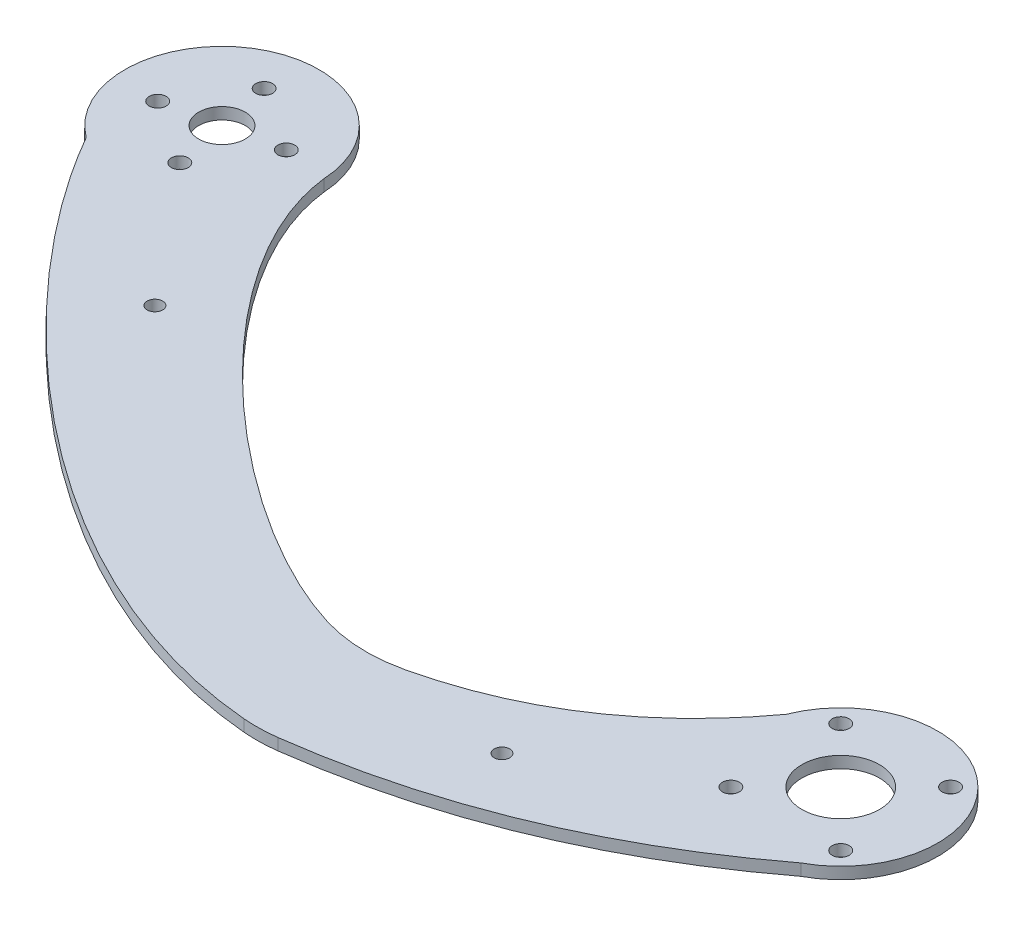
SolidWorks part; units mm, degrees
material "1060 Alloy"
ref_plane "Front" through (0, 0, 0) normal (0, 0, 1) x (1, 0, 0)
ref_plane "Top" through (0, 0, 0) normal (0, 1, 0) x (1, 0, 0)
ref_plane "Right" through (0, 0, 0) normal (1, 0, 0) x (0, 0, -1)
sketch "Sketch2" plane through (0, 0, 0) normal (0, 1, 0) x (1, 0, 0)
  point P0 (0, 0)
  line B0 (-70.9851, 36.1523) -> (-113.5823, 33.9244)
  arc B1 (5.8927, -11.0239) -> (-11.6176, 4.6132) centre (0, 0) ccw
  arc B2 (-101.0993, 34.5773) -> (-120.9882, 23.8546) centre (-113.5823, 33.9244) ccw
  spline B3 degree 3 poles (-44.5149, -15.6481) (-60.4932, -16.621) (-98.7194, 13.994) (-101.0993, 34.5773) knots 0 0 0 0 1 1 1 1
  spline B4 degree 2 poles (5.8927, -11.0239) (-16.2083, -27.8197) (-43.715, -30.9419) knots 0 0 0 1 1 1
  spline B5 degree 3 poles (-43.715, -30.9419) (-74.6559, -29.7722) (-107.9347, 0.9093) (-120.9882, 23.8546) knots 0 0 0 0 1 1 1 1
  spline B6 degree 2 poles (-44.5149, -15.6481) (-23.755, -12.0499) (-11.6176, 4.6132) knots 0 0 0 1 1 1
sketch_block_instance "Block5-1"
sketch_block "Block5" parameters "D1"=25, "D14"=79.1954, "D15"=48.0238, "D17"=92.8889, "D18"=42.1388, "D19"=62.1612, "D2"=5.3089, "D3"=16.6697, "D4"=25.1002, "D5"=50.5803, "D6"=74.3089, "D7"=104.4643, "D8"=116.9643, "D9"=124.8861, "D10"=135.8089, "D11"=34.5967, "D12"=39.8104, "D13"=51.127, "D16"=68.4269
extrude "Boss-Extrude1" add sketch "Sketch2" along normal blind 1.5 contours B5 B4 B1 B6 B3 B2 region at (-18.1336, 0, 22.9214)
fillet "Fillet2" radius 20 1 edges at (-44.5149, 0.75, 15.6481)
fillet "Fillet3" radius 20 1 edges at (-43.715, 0.75, 30.9419)
ref_plane "Plane1" through (0, 1.5, 0) normal (0, 1, 0) x (1, 0, 0)
sketch "Sketch3" plane through (0, 1.5, 0) normal (0, 1, 0) x (1, 0, 0)
  line L0 (0, 0) -> (0, 56.3072) construction
  line L1 (-7.0711, 7.0711) -> (0, 0) construction
  line L2 (-113.5823, 33.9244) -> (0, 0) construction
  line L3 (-56.7911, 16.9622) -> (-30.8992, 103.6508) construction
  line L4 (-103.7915, 35.9592) -> (-113.5823, 33.9244) construction
  line L5 (-115.6171, 43.7152) -> (-113.5823, 33.9244) construction
  line L6 (-103.7915, 35.9592) -> (-113.5823, 33.9244) construction
  line L7 (-111.5474, 24.1336) -> (-113.5823, 33.9244) construction
  line L8 (-123.3731, 31.8896) -> (-113.5823, 33.9244) construction
  circle A0 centre (0, 0) radius 5
  circle A1 centre (-7.0711, 7.0711) radius 1.09
  circle A2 centre (7.0711, 7.0711) radius 1.09
  circle A3 centre (7.0711, -7.0711) radius 1.09
  circle A4 centre (-7.0711, -7.0711) radius 1.09
  circle A5 centre (-113.5823, 33.9244) radius 3
  circle A6 centre (-106.7287, 35.3488) radius 1.09
  circle A7 centre (-112.1579, 27.0709) radius 1.09
  circle A8 centre (-120.4358, 32.5001) radius 1.09
  circle A10 centre (-115.0066, 40.778) radius 1.09
  point P8 (-56.7911, 16.9622)
  point P15 (0, 0)
  point P35 (-113.5823, 33.9244)
  dimension "D1" = 10
  dimension "D2" = 2.18
  dimension "D6" = 6
  dimension "D7" = 2.18
  dimension "D8" = 7
  dimension "D3" = 45
  dimension "D4" = 10
  dimension "D5" = 4
  dimension "D9" = 4
extrude "Cut-Extrude2" cut sketch "Sketch3" against normal blind 10
sketch "Sketch4" plane through (0, 1.5, 0) normal (0, 1, 0) x (1, 0, 0)
  line L0 (-113.5823, 33.9244) -> (-69.4661, -34.4033) construction
  line L1 (0, 0) -> (-63.0101, -44.4968) construction
  circle A0 centre (-97.8402, 9.543) radius 1
  circle A1 centre (-25.5617, -18.0513) radius 1
  dimension "D1" = 2
  dimension "D2" = 25.5617
  dimension "D3" = 97.8402
  dimension "D4" = 9.543
  dimension "D5" = 18.0513
extrude "Cut-Extrude3" cut sketch "Sketch4" against normal blind 10
